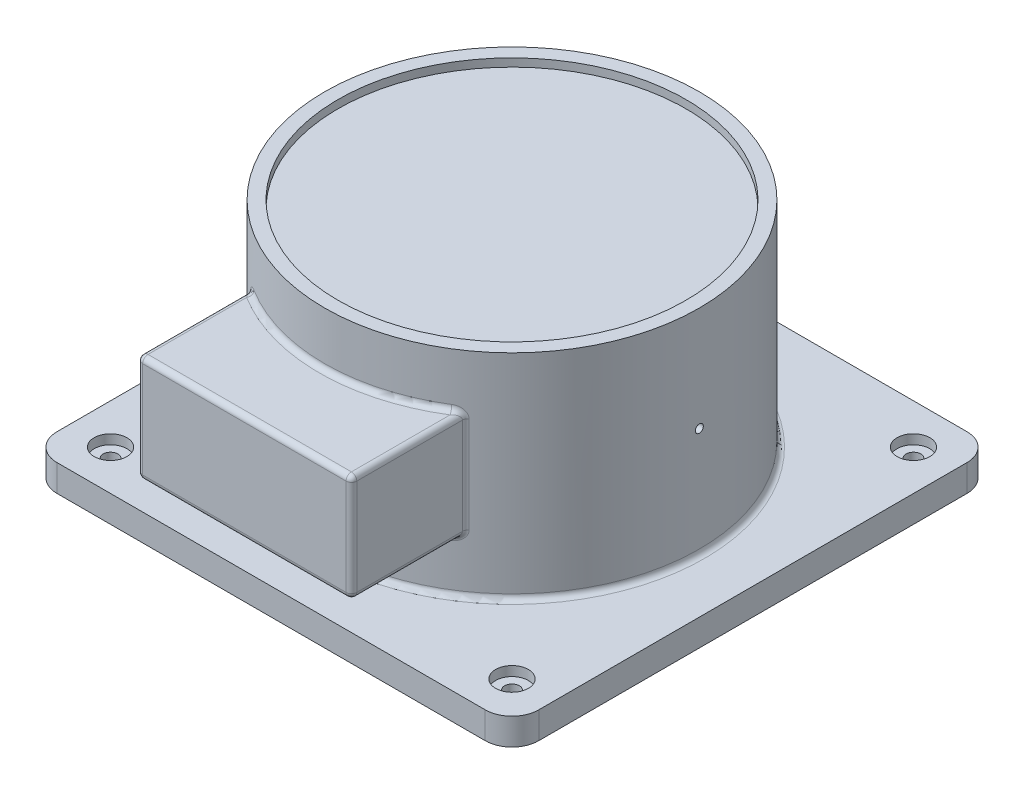
SolidWorks part; units mm, degrees
material "1060 Alloy"
ref_plane "Front Plane" through (0, 0, 0) normal (0, 0, 1) x (1, 0, 0)
ref_plane "Top Plane" through (0, 0, 0) normal (0, 1, 0) x (1, 0, 0)
ref_plane "Right Plane" through (0, 0, 0) normal (1, 0, 0) x (0, 0, -1)
sketch "Sketch1" plane through (0, 0, 0) normal (0, 1, 0) x (1, 0, 0)
  line L1 (-90, -90) -> (90, -90)
  line L2 (-90, -90) -> (-90, 90)
  line L3 (-90, 90) -> (90, 90)
  line L4 (90, -90) -> (90, 90)
  line L5 (-90, -90) -> (90, 90) construction
  line L6 (-90, 90) -> (90, -90) construction
  point P0 (0, 0)
  dimension "D1" = 180
extrude "Boss-Extrude1" add sketch "Sketch1" along normal blind 10
sketch "Sketch2" plane through (0, 10, 0) normal (0, 1, 0) x (1, 0, 0)
  circle A0 centre (0, 0) radius 70
  dimension "D1" = 140
extrude "Boss-Extrude2" add sketch "Sketch2" along normal blind 80
sketch "Sketch4" plane through (0, 0, 0) normal (0, 0, 1) x (1, 0, 0)
  line L1 (-40, 30) -> (40, 30)
  line L2 (-40, 30) -> (-40, 70)
  line L3 (-40, 70) -> (40, 70)
  line L4 (40, 30) -> (40, 70)
  line L5 (-40, 30) -> (40, 70) construction
  line L6 (-40, 70) -> (40, 30) construction
  point P0 (0, 50)
  dimension "D1" = 80
  dimension "D2" = 40
  dimension "D3" = 50
extrude "Boss-Extrude3" add sketch "Sketch4" along normal blind 100
sketch "Sketch5" plane through (0, 90, 0) normal (0, 1, 0) x (1, 0, 0)
  circle A2 centre (0, 0) radius 65
  circle A3 centre (0, 0) radius 65
  dimension "D1" = 5
extrude "Cut-Extrude1" cut sketch "Sketch5" against normal blind 3
hole_wizard "CBORE for M5 Hex Head Bolt1" positions "Sketch6" profile "Sketch7" counterbore size "M5" standard "ANSI Metric" end condition through all
sketch "Sketch6" plane through (0, 10, 0) normal (0, 1, 0) x (1, 0, 0)
  point P35 (75, -75)
  point P37 (-75, -75)
  point P39 (-75, 75)
  point P41 (75, 75)
  dimension "D1" = 150
  dimension "D2" = 150
  dimension "D3" = 75
  dimension "D5" = 75
sketch "Sketch7" plane through (75, 10, 75) normal (1, 0, 0) x (0, 0, 1)
  line L0 (0, 0) -> (0, 10)
  line L1 (0, 10) -> (2.75, 10)
  line L3 (2.75, 10) -> (2.75, 3.58)
  line L4 (2.75, 3.58) -> (6.12, 3.58)
  line L5 (6.12, 3.58) -> (6.12, 0)
  line L7 (6.12, 0) -> (0, 0)
  line L11 (0, -6.35) -> (0, 107.95) construction
  dimension "Thru Hole Dia." = 5.5
  dimension "Thru Hole Depth" = 10
  dimension "C'Bore Dia." = 12.24
  dimension "C'Bore Depth" = 3.58
fillet "Fillet2" radius 10 4 edges at (-90, 5, 90) (-90, 5, -90) (90, 5, -90) (90, 5, 90)
fillet "Fillet3" radius 2 13 edges at (40, 50, 100) (0, 70, 100) (0, 10, 70) (-40, 70, 78.7228) (-40, 30, 78.7228) (40, 30, 78.7228) (40, 70, 78.7228) (-40, 50, 57.4456) (0, 30, 70) (40, 50, 57.4456) (0, 70, 70) (-40, 50, 100) (0, 30, 100)
sketch "Sketch9" plane through (0, 0, 0) normal (1, 0, 0) x (0, 0, -1)
  line L0 (70, 12) -> (70, 90) construction
  line L1 (70, 12) -> (70, 90) construction
  circle A0 centre (0, 51) radius 1.5
  point P8 (70, 51)
  dimension "D1" = 3
extrude "Cut-Extrude2" cut sketch "Sketch9" along normal up to next from offset 50
